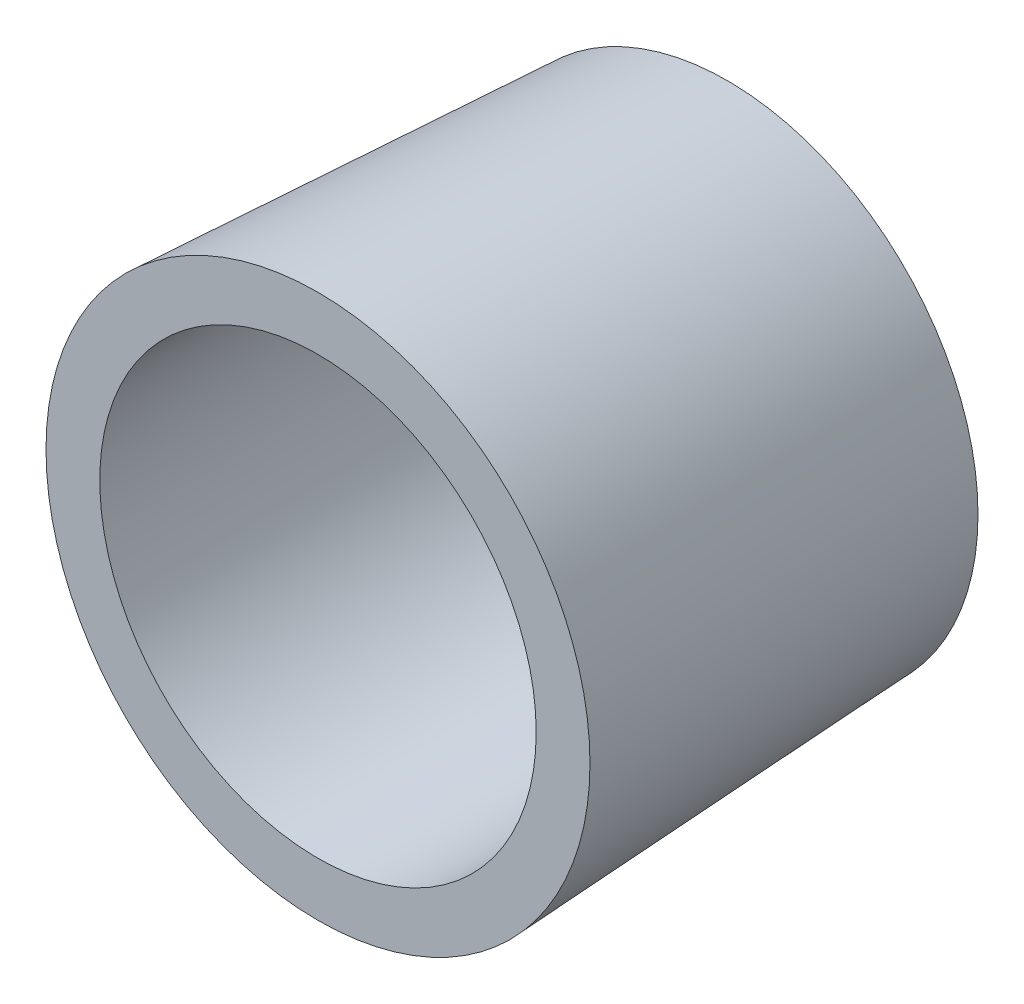
SolidWorks part; units mm, degrees
ref_plane "Front Plane" through (0, 0, 0) normal (0, 0, 1) x (1, 0, 0)
ref_plane "Top Plane" through (0, 0, 0) normal (0, 1, 0) x (1, 0, 0)
ref_plane "Right Plane" through (0, 0, 0) normal (1, 0, 0) x (0, 0, -1)
sketch "Sketch1" plane through (0, 0, 0) normal (0, 0, 1) x (1, 0, 0)
  circle A2 centre (0, 0) radius 23.25
  circle A3 centre (0, 0) radius 20.25
  circle A4 centre (0, 0) radius 17
  dimension "D1" = 40.5
  dimension "D2" = 3
  dimension "D3" = 34
extrude "Boss-Extrude1" add sketch "Sketch1" against normal blind 3 contours A3 A4 | A2 A3 | A4 region at (-22.5924, 0, 0) region at (-19.6772, 0, 0) region at (0, 0, 0)
extrude "Boss-Extrude2" add sketch "Sketch1<3>" along normal blind 35 contours A2 A3 region at (-22.5924, 0, 0)
sketch "Sketch1<3>" plane through (0, 0, 0) normal (0, 0, 1) x (1, 0, 0) same geometry as "Sketch1"
sketch "Sketch4" plane through (0, 0, 0) normal (0, 1, 0) x (1, 0, 0)
  line L0 (23.25, -35) -> (23.25, 3)
  line L1 (-23.25, -35) -> (23.25, -35) construction
  line L5 (23.25, 3) -> (25.2415, -35)
  line L6 (25.2415, -35) -> (23.25, -35)
  line L7 (0, 0) -> (0, -35) construction
  line L8 (0, -35) -> (23.25, -35) construction
  point P4 (23.25, -0.7668)
  point P5 (0, 0)
  dimension "D1" = 3
revolve "Revolve2" add sketch "Sketch4" angle 360 about L7
sketch "Sketch6" plane through (0, 0, 0) normal (0, 0, 1) x (1, 0, 0)
  line L0 (3.5, -1.5) -> (3.5, 1.5)
  line L1 (-1.5, -1.5) -> (1.5, -1.5)
  line L2 (-1.5, -1.5) -> (-1.5, 1.5)
  line L3 (-1.5, 1.5) -> (1.5, 1.5)
  line L4 (1.5, -1.5) -> (1.5, 1.5)
  line L5 (-1.5, -1.5) -> (1.5, 1.5) construction
  line L6 (-1.5, 1.5) -> (1.5, -1.5) construction
  line L7 (3.5, -1.5) -> (6.5, -1.5)
  line L8 (6.5, -1.5) -> (6.5, 1.5)
  line L9 (3.5, 1.5) -> (6.5, 1.5)
  line L10 (8.5, -1.5) -> (8.5, 1.5)
  line L11 (8.5, -1.5) -> (11.5, -1.5)
  line L12 (11.5, -1.5) -> (11.5, 1.5)
  line L13 (8.5, 1.5) -> (11.5, 1.5)
  line L14 (3.5, 3.5) -> (3.5, 6.5)
  line L15 (3.5, 3.5) -> (6.5, 3.5)
  line L16 (6.5, 3.5) -> (6.5, 6.5)
  line L17 (3.5, 6.5) -> (6.5, 6.5)
  line L18 (8.5, 3.5) -> (8.5, 6.5)
  line L19 (8.5, 3.5) -> (11.5, 3.5)
  line L20 (11.5, 3.5) -> (11.5, 6.5)
  line L21 (8.5, 6.5) -> (11.5, 6.5)
  line L22 (3.5, 8.5) -> (3.5, 11.5)
  line L23 (3.5, 8.5) -> (6.5, 8.5)
  line L24 (6.5, 8.5) -> (6.5, 11.5)
  line L25 (3.5, 11.5) -> (6.5, 11.5)
  line L26 (8.5, 8.5) -> (8.5, 11.5)
  line L27 (8.5, 8.5) -> (11.5, 8.5)
  line L28 (11.5, 8.5) -> (11.5, 11.5)
  line L29 (8.5, 11.5) -> (11.5, 11.5)
  line L30 (-1.5, 3.5) -> (-1.5, 6.5)
  line L31 (-1.5, 3.5) -> (1.5, 3.5)
  line L32 (1.5, 3.5) -> (1.5, 6.5)
  line L33 (-1.5, 6.5) -> (1.5, 6.5)
  line L34 (-1.5, 8.5) -> (-1.5, 11.5)
  line L35 (-1.5, 8.5) -> (1.5, 8.5)
  line L36 (1.5, 8.5) -> (1.5, 11.5)
  line L37 (-1.5, 11.5) -> (1.5, 11.5)
  line L38 (20.9, 0) -> (-20.9, 0) construction
  line L39 (-1.5, -8.5) -> (1.5, -8.5)
  line L40 (1.5, -8.5) -> (1.5, -11.5)
  line L41 (-1.5, -11.5) -> (1.5, -11.5)
  line L42 (-1.5, -8.5) -> (-1.5, -11.5)
  line L43 (3.5, -8.5) -> (6.5, -8.5)
  line L44 (6.5, -8.5) -> (6.5, -11.5)
  line L45 (3.5, -11.5) -> (6.5, -11.5)
  line L46 (3.5, -8.5) -> (3.5, -11.5)
  line L47 (8.5, -8.5) -> (11.5, -8.5)
  line L48 (11.5, -8.5) -> (11.5, -11.5)
  line L49 (8.5, -11.5) -> (11.5, -11.5)
  line L50 (8.5, -8.5) -> (8.5, -11.5)
  line L51 (8.5, -3.5) -> (11.5, -3.5)
  line L52 (11.5, -3.5) -> (11.5, -6.5)
  line L53 (8.5, -6.5) -> (11.5, -6.5)
  line L54 (8.5, -3.5) -> (8.5, -6.5)
  line L55 (3.5, -3.5) -> (6.5, -3.5)
  line L56 (6.5, -3.5) -> (6.5, -6.5)
  line L57 (3.5, -6.5) -> (6.5, -6.5)
  line L58 (3.5, -3.5) -> (3.5, -6.5)
  line L59 (-1.5, -3.5) -> (1.5, -3.5)
  line L60 (1.5, -3.5) -> (1.5, -6.5)
  line L61 (-1.5, -6.5) -> (1.5, -6.5)
  line L62 (-1.5, -3.5) -> (-1.5, -6.5)
  line L63 (0, -20.9) -> (0, 20.9) construction
  line L64 (-8.5, -8.5) -> (-8.5, -11.5)
  line L65 (-8.5, -11.5) -> (-11.5, -11.5)
  line L66 (-11.5, -8.5) -> (-11.5, -11.5)
  line L67 (-8.5, -8.5) -> (-11.5, -8.5)
  line L68 (-3.5, -8.5) -> (-3.5, -11.5)
  line L69 (-3.5, -11.5) -> (-6.5, -11.5)
  line L70 (-6.5, -8.5) -> (-6.5, -11.5)
  line L71 (-3.5, -8.5) -> (-6.5, -8.5)
  line L72 (-3.5, -3.5) -> (-3.5, -6.5)
  line L73 (-3.5, -6.5) -> (-6.5, -6.5)
  line L74 (-6.5, -3.5) -> (-6.5, -6.5)
  line L75 (-3.5, -3.5) -> (-6.5, -3.5)
  line L76 (-8.5, -3.5) -> (-8.5, -6.5)
  line L77 (-8.5, -6.5) -> (-11.5, -6.5)
  line L78 (-11.5, -3.5) -> (-11.5, -6.5)
  line L79 (-8.5, -3.5) -> (-11.5, -3.5)
  line L80 (-8.5, -1.5) -> (-11.5, -1.5)
  line L81 (-11.5, -1.5) -> (-11.5, 1.5)
  line L82 (-8.5, 1.5) -> (-11.5, 1.5)
  line L83 (-8.5, -1.5) -> (-8.5, 1.5)
  line L84 (-3.5, -1.5) -> (-6.5, -1.5)
  line L85 (-6.5, -1.5) -> (-6.5, 1.5)
  line L86 (-3.5, 1.5) -> (-6.5, 1.5)
  line L87 (-3.5, -1.5) -> (-3.5, 1.5)
  line L88 (-3.5, 3.5) -> (-6.5, 3.5)
  line L89 (-6.5, 3.5) -> (-6.5, 6.5)
  line L90 (-3.5, 6.5) -> (-6.5, 6.5)
  line L91 (-3.5, 3.5) -> (-3.5, 6.5)
  line L92 (-8.5, 3.5) -> (-11.5, 3.5)
  line L93 (-11.5, 3.5) -> (-11.5, 6.5)
  line L94 (-8.5, 6.5) -> (-11.5, 6.5)
  line L95 (-8.5, 3.5) -> (-8.5, 6.5)
  line L96 (-8.5, 8.5) -> (-11.5, 8.5)
  line L97 (-11.5, 8.5) -> (-11.5, 11.5)
  line L98 (-8.5, 11.5) -> (-11.5, 11.5)
  line L99 (-8.5, 8.5) -> (-8.5, 11.5)
  line L100 (-3.5, 8.5) -> (-6.5, 8.5)
  line L101 (-6.5, 8.5) -> (-6.5, 11.5)
  line L102 (-3.5, 11.5) -> (-6.5, 11.5)
  line L103 (-3.5, 8.5) -> (-3.5, 11.5)
  circle A1 centre (0, 0) radius 20.25
  circle A2 centre (0, 0) radius 20.25 construction
  point P65 (-1.048, 6.4483)
  dimension "D2" = 3
  dimension "D5" = 2
  dimension "D6" = 2
  dimension "D1" = 0
  dimension "D3" = 3
  dimension "D4" = 3
extrude "Cut-Extrude1" cut sketch "Sketch6" against normal through all contours L96 L99 L98 L97 | L100 L103 L102 L101 | L37 L34 L35 L36 | L25 L22 L23 L24 | L29 L26 L27 L28 | L21 L18 L19 L20 | L17 L14 L15 L16 | L33 L30 L31 L32 | L88 L91 L90 L89 | L92 L95 L94 L93 | L80 L83 L82 L81 | L76 L79 L78 L77 | L84 L87 L86 L85 | L72 L75 L74 L73 | L1 L4 L3 L2 | L9 L0 L7 L8 | L13 L10 L11 L12 | L51 L54 L53 L52 | L55 L58 L57 L56 | L59 L62 L61 L60 | L64 L67 L66 L65 | L68 L71 L70 L69 | L39 L42 L41 L40 | L43 L46 L45 L44 | L47 L50 L49 L48 region at (5, 0, 0) region at (0, 0, 0) region at (10, 0, 0) region at (5, 5, 0) region at (10, 5, 0) region at (5, 10, 0) region at (10, 10, 0) region at (0, 5, 0) region at (0, 10, 0) region at (0, -10, 0) region at (5, -10, 0) region at (10, -10, 0) region at (10, -5, 0) region at (5, -5, 0) region at (0, -5, 0) region at (-10, -10, 0) region at (-5, -10, 0) region at (-5, -5, 0) region at (-10, -5, 0) region at (-10, 0, 0) region at (-5, 0, 0) region at (-5, 5, 0) region at (-10, 5, 0) region at (-10, 10, 0) region at (-5, 10, 0)
